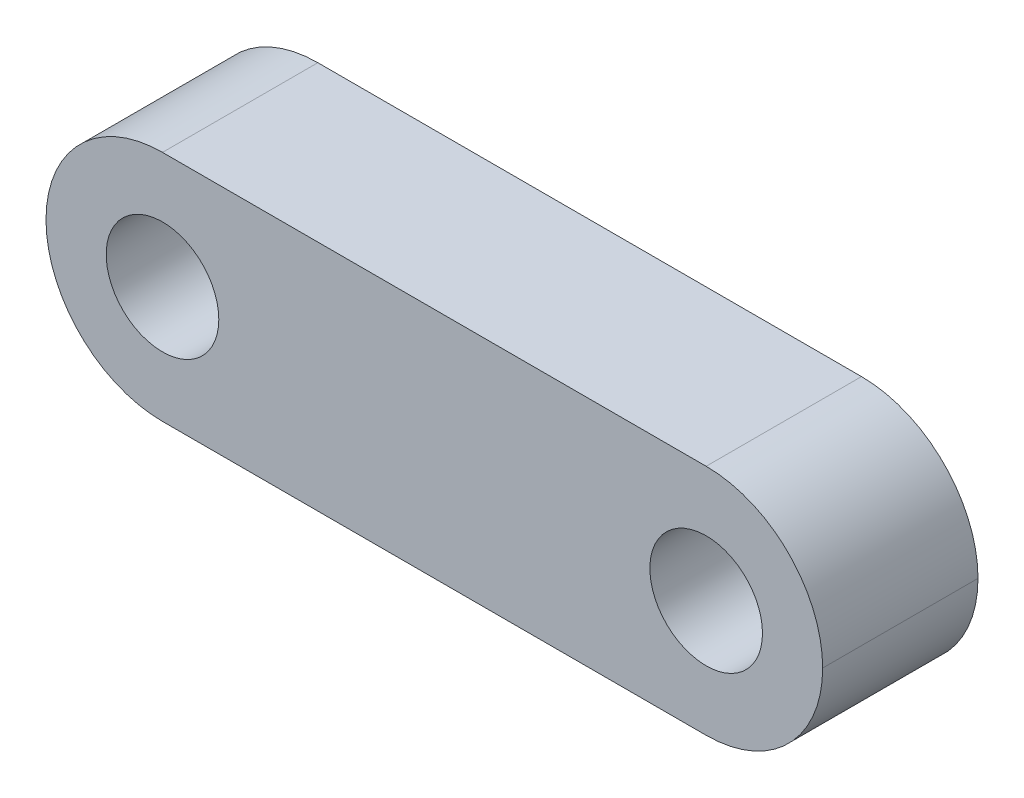
SolidWorks part; units mm, degrees
ref_plane "Front" through (0, 0, 0) normal (0, 0, 1) x (1, 0, 0)
ref_plane "Top" through (0, 0, 0) normal (0, 1, 0) x (1, 0, 0)
ref_plane "Right" through (0, 0, 0) normal (1, 0, 0) x (0, 0, -1)
sketch "Sketch1" plane through (0, 0, 0) normal (0, 0, 1) x (1, 0, 0)
  line L1 (0, 0) -> (20, 0)
  line L2 (0, 0) -> (0, -6)
  line L3 (0, -6) -> (20, -6)
  line L4 (20, 0) -> (20, -6)
  dimension "D1" = 6
  dimension "D2" = 20
extrude "Boss-Extrude1" add sketch "Sketch1" along normal blind 4
sketch "Sketch2" plane through (0, 0, 4) normal (0, 0, 1) x (1, 0, 0)
  line L0 (0, 0) -> (0, -6) construction
  line L1 (20, -6) -> (20, 0) construction
  circle A0 centre (3, -3) radius 1.45
  circle A1 centre (17, -3) radius 1.45
  dimension "D1" = 2.9
  dimension "D3" = 2.9
  dimension "D2" = 3
  dimension "D4" = 3
extrude "Cut-Extrude1" cut sketch "Sketch2" against normal through all and the other way through all
fillet "Fillet1" radius 3 4 edges at (20, -6, 2) (20, 0, 2) (0, -6, 2) (0, 0, 2)
